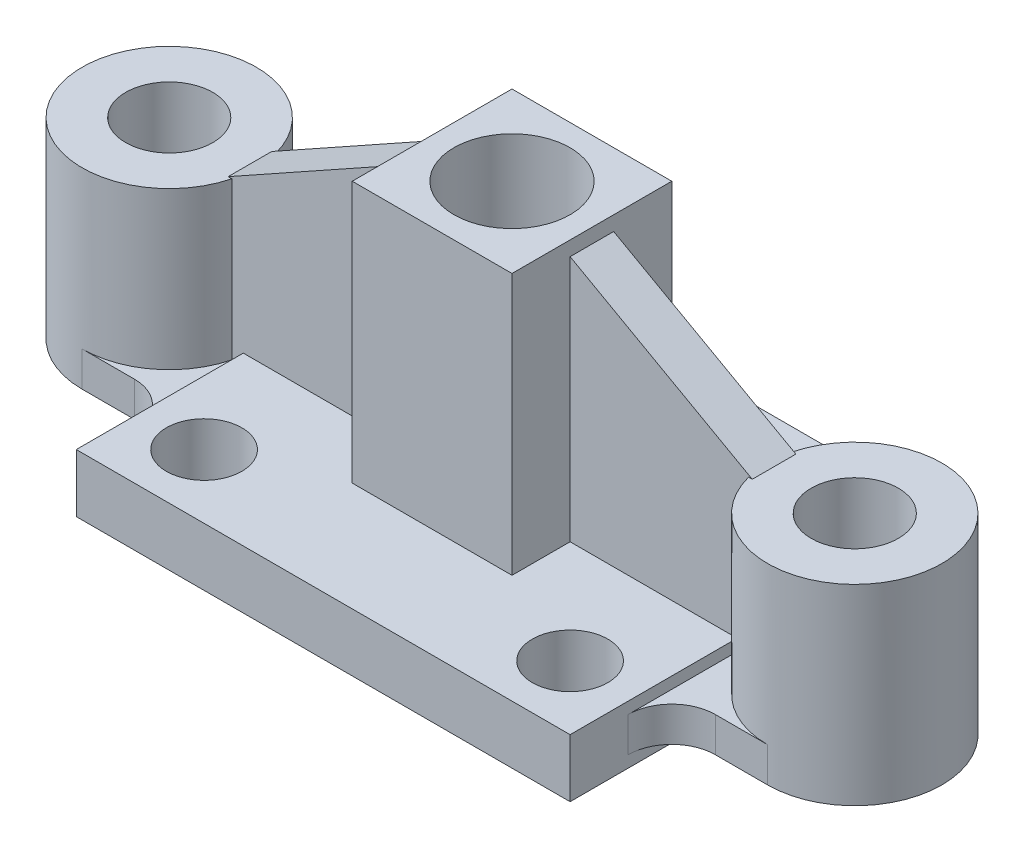
SolidWorks part; units mm, degrees
ref_plane "Front Plane" through (0, 0, 0) normal (0, 0, 1) x (1, 0, 0)
ref_plane "Top Plane" through (0, 0, 0) normal (0, 1, 0) x (1, 0, 0)
ref_plane "Right Plane" through (0, 0, 0) normal (1, 0, 0) x (0, 0, -1)
sketch "Sketch1" plane through (0, 0, 0) normal (0, 0, 1) x (1, 0, 0)
  line L1 (-85, 10) -> (85, 10)
  line L2 (-85, 10) -> (-85, -10)
  line L3 (-85, -10) -> (85, -10)
  line L4 (85, 10) -> (85, -10)
  line L5 (-85, 10) -> (85, -10) construction
  line L6 (-85, -10) -> (85, 10) construction
  point P0 (0, 0)
  dimension "D1" = 170
  dimension "D2" = 20
extrude "Boss-Extrude1" add sketch "Sketch1" against normal blind 130
sketch "Sketch2" plane through (0, 0, 0) normal (0, 1, 0) x (1, 0, 0)
  line L0 (0, 0) -> (0, 130) construction
  line L1 (85, 130) -> (-85, 130) construction
  line L2 (-85, 130) -> (85, 130)
  line L3 (-27.5, 92.5) -> (27.5, 92.5)
  line L4 (-27.5, 92.5) -> (-27.5, 37.5)
  line L5 (-27.5, 37.5) -> (27.5, 37.5)
  line L6 (27.5, 92.5) -> (27.5, 37.5)
  line L7 (-27.5, 92.5) -> (27.5, 37.5) construction
  line L8 (-27.5, 37.5) -> (27.5, 92.5) construction
  line L9 (85, 0) -> (-85, 0)
  line L12 (118, 95) -> (100, 95)
  line L18 (-118, 95) -> (-100, 95)
  line L19 (-118, 35) -> (-100, 35)
  line L20 (-85, 110) -> (-85, 130)
  line L22 (-85, 20) -> (-85, 0)
  line L23 (118, 35) -> (100, 35)
  line L24 (85, 130) -> (85, 110)
  line L26 (85, 20) -> (85, 0)
  circle A0 centre (0, 65) radius 20
  circle A1 centre (-118, 65) radius 30
  circle A2 centre (-118, 65) radius 15
  arc A3 (-100, 35) -> (-85, 20) centre (-100, 20) cw
  arc A4 (-85, 110) -> (-100, 95) centre (-100, 110) cw
  circle A5 centre (118, 65) radius 30
  circle A6 centre (118, 65) radius 15
  arc A7 (85, 20) -> (100, 35) centre (100, 20) cw
  arc A8 (85, 110) -> (100, 95) centre (100, 110) ccw
  point P5 (0, 65)
  dimension "D3" = 40
  dimension "D7" = 60
  dimension "D8" = 30
  dimension "D9" = 15
  dimension "D12" = 60
  dimension "D13" = 30
  dimension "D14" = 15
  dimension "D1" = 55
  dimension "D2" = 55
extrude "Boss-Extrude3" add sketch "Sketch2" along normal blind 60 and the other way blind 6 separate body contours A1 A2 | A5 A6 region at (-97.3868, 0, -85.6132) region at (138.6132, 0, -85.6132)
extrude "Boss-Extrude4" add sketch "Sketch2<4>" along normal blind 6 and the other way blind 6 contours A8 L24 L2 L20 A4 L18 A1 L19 A3 L22 L9 L26 A7 L23 A5 L12 L3 L6 L5 L4 region at (0, 0, -127.3056)
sketch "Sketch2<4>" plane through (0, 0, 0) normal (0, 1, 0) x (1, 0, 0) same geometry as "Sketch2"
extrude "Boss-Extrude5" add sketch "Sketch2<5>" along normal blind 100 contours L6 L5 L4 L3 | A0
sketch "Sketch2<5>" plane through (0, 0, 0) normal (0, 1, 0) x (1, 0, 0) same geometry as "Sketch2"
ref_plane "Plane1" through (0, 0, -65) normal (0, 0, 1) x (1, 0, 0)
sketch "Sketch3" plane through (0, 0, -65) normal (0, 0, 1) x (1, 0, 0)
  line L0 (-27.5, 95) -> (-90.22, 60)
  line L6 (-27.5, 100) -> (-27.5, 10) construction
  line L7 (-88, 60) -> (-148, 60) construction
  dimension "D1" = 5
rib "Rib10" sketch "Sketch3" sketch "Sketch3" thickness 15 extrusion direction parallel to sketch draft on no parameters "D1"=15
mirror "Mirror1" about plane through (0, 0, 0) normal (1, 0, 0) of "Rib10"
sketch "Sketch4" plane through (0, 10, 0) normal (0, 1, 0) x (1, 0, 0)
  line L0 (-85, 130) -> (-85, 72.5) construction
  line L1 (85, 130) -> (-85, 130) construction
  line L2 (85, 130) -> (85, 72.5) construction
  line L3 (-85, 57.5) -> (-85, 0) construction
  line L4 (85, 0) -> (-85, 0) construction
  line L5 (85, 57.5) -> (85, 0) construction
  circle A0 centre (-63, 108) radius 13
  circle A1 centre (63, 108) radius 13
  circle A2 centre (-63, 22) radius 13
  circle A3 centre (63, 22) radius 13
  dimension "D3" = 26
  dimension "D1" = 22
  dimension "D2" = 22
  dimension "D4" = 22
  dimension "D5" = 22
  dimension "D6" = 22
  dimension "D7" = 22
  dimension "D8" = 22
  dimension "D9" = 22
extrude "Cut-Extrude1" cut sketch "Sketch4" against normal through all
